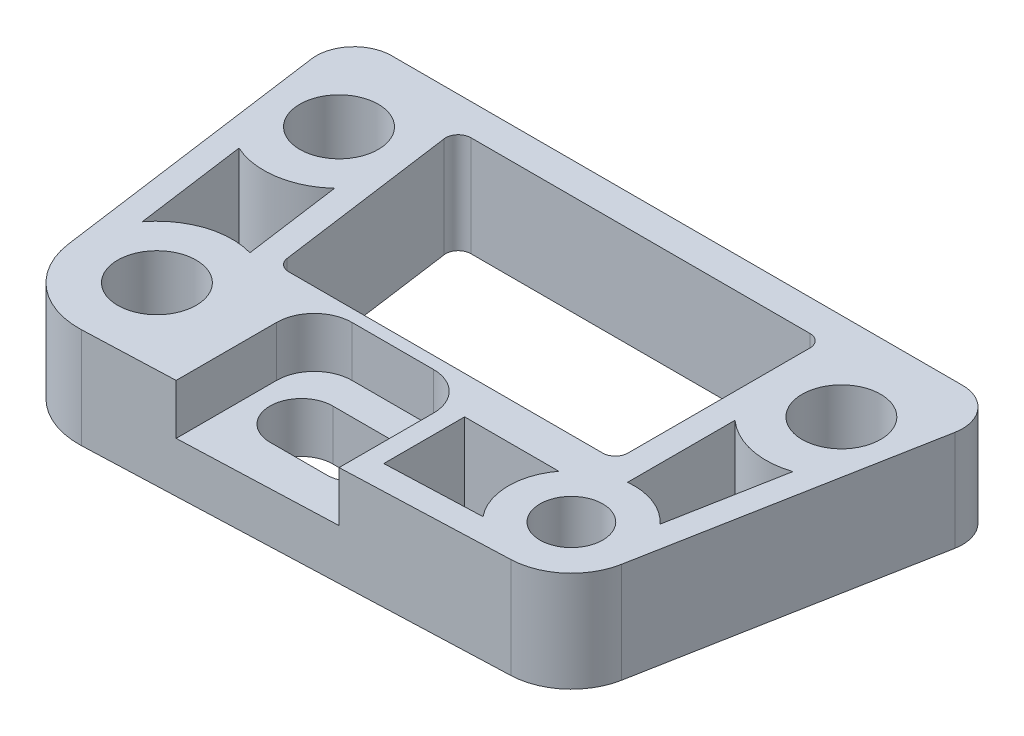
SolidWorks part; units mm, degrees
note: '?' marks a value the reader was unsure of.
material "7075-T6 (SN)"
ref_plane "X-Y Datum" through (0, 0, 0) normal (0, 0, 1) x (1, 0, 0)
ref_plane "X-Z Datum" through (0, 0, 0) normal (0, 1, 0) x (1, 0, 0)
ref_plane "Y-Z Datum" through (0, 0, 0) normal (1, 0, 0) x (0, 0, -1)
other "Graphic1"
other "Graphic (Closed) -1"
other "Graphic2"
other "Graphic (Closed) -2"
sketch "Sketch1" plane through (0, 0, 0) normal (0, 1, 0) x (1, 0, 0)
  line L0 (38.1, -5.08) -> (6.099, -5.08)
  line L1 (54.2925, 13.97) -> (-12.3825, 13.97) construction
  line L4 (54.2925, 31.75) -> (-12.3825, 31.75)
  line L6 (46.355, 22.86) -> (-4.445, 22.86) construction
  line L7 (54.2925, 31.75) -> (54.2925, 13.97)
  line L8 (-12.3825, 31.75) -> (-12.3825, 13.97)
  line L19 (48.26, 0) -> (54.2925, 13.97)
  line L21 (-7.9375, 0) -> (-12.3825, 13.97)
  line L28 (17.1395, -0.1867) -> (14.8786, 3.0422)
  line L30 (16.5708, 1.8211) -> (13.97, 0) construction
  line L31 (16.009, 1.4277) -> (11.1341, 1.4277) construction
  circle A0 centre (0, 0) radius 3.9688
  circle A1 centre (41.91, 0) radius 3.175
  circle A2 centre (46.355, 22.86) radius 3.9688
  circle A3 centre (-4.445, 22.86) radius 3.9687
  arc A4 (48.26, 0) -> (38.1, -5.08) centre (41.91, 0) cw
  arc A5 (6.099, -5.08) -> (-7.9375, 0) centre (0, 0) cw
  arc A12 (17.1395, -0.1867) -> (14.8786, 3.0422) centre (13.97, 0) cw
  point P22 (16.009, 1.4277)
  dimension "D2" = 6.35
  dimension "D7" = 7.9375
  dimension "D8" = 6.35
  dimension "D12" = 0.6858
  dimension "D10" = 7.9375
  dimension "D17" = 35
  dimension "D19" = 7.9375
  dimension "D18" = 19.05
  dimension "D14" = 3.9418
  dimension "D20" = 7.9375
  dimension "D3" = 50.8
  dimension "D4" = 17.78
  dimension "D5" = 8.89
  dimension "D6" = 31.75
  dimension "D9" = 41.91
  dimension "D11" = 7.9375
  dimension "D13" = 3.175
  dimension "D15" = 13.97
  dimension "D16" = 5.08
  dimension "D21" = 4.445
  dimension "D22" = 66.644
  dimension "D23" = 72.35
extrude "Boss-Extrude1" [suppressed] add sketch "Sketch1" against normal blind 10.16
sketch "Sketch2" [suppressed] plane through (0, 0, 0) normal (0, -1, 0) x (1, 0, 0)
  line L0 (9.2075, 0) -> (9.2075, 5.08)
  line L1 (6.099, 5.08) -> (38.1, 5.08) construction
  line L2 (9.2075, 5.08) -> (18.7325, 5.08)
  line L3 (18.7325, 5.08) -> (18.7325, 0)
  arc A0 (9.2075, 0) -> (18.7325, 0) centre (13.97, 0) ccw
  dimension "D1" = 9.525
extrude "Cut-Extrude1" [suppressed] cut sketch "Sketch2" along normal blind 5.08
ref_point "Point1" [suppressed]
ref_point "Point2" [suppressed]
ref_axis "Axis4" [suppressed] through (0, -10.16, 0) along (0, 1, 0)?
sketch "Sketch3" plane through (0, 0, 0) normal (0, 1, 0) x (1, 0, 0)
  line L0 (14.605, 0) -> (11.43, 0) construction
  line L1 (17.7745, -0.1867) -> (15.5136, 3.0422) construction
  line L2 (16.644, 1.4277) -> (14.605, 0) construction
  line L3 (54.2925, 31.75) -> (-12.3825, 31.75)
  line L5 (-12.3825, 13.97) -> (54.2925, 13.97) construction
  line L10 (54.2925, 22.86) -> (46.355, 22.86) construction
  line L11 (46.355, 22.86) -> (-4.445, 22.86) construction
  line L12 (-4.445, 22.86) -> (-12.3825, 22.86) construction
  line L18 (38.735, 8.89) -> (38.735, 27.305)
  line L19 (37.465, 28.575) -> (3.175, 28.575)
  line L20 (1.9169, 27.1318) -> (4.4516, 8.7168)
  line L21 (5.7097, 7.62) -> (37.465, 7.62)
  line L25 (20.32, 0) -> (14.605, 0) construction
  line L26 (20.32, 3.175) -> (14.605, 3.175)
  line L28 (20.32, -3.175) -> (14.605, -3.175)
  line L29 (23.4895, -0.1867) -> (21.2286, 3.0422)
  line L30 (20.32, 0) -> (22.359, 1.4277) construction
  line L31 (42.1505, -6.3454) -> (0.3007, -7.9318)
  line L36 (-7.8634, -1.0823) -> (-12.3825, 31.75)
  line L42 (46.587, 4.2951) -> (48.6976, 15.609)
  line L44 (41.275, 17.1804) -> (41.275, 6.3182)
  line L45 (-6.0805, 4.5926) -> (-7.6429, 15.9435)
  line L46 (2.0783, 7.3311) -> (0.7129, 17.2511)
  line L47 (36.978, -3.9997) -> (27.305, -4.3664)
  line L48 (36.83, 3.81) -> (27.305, 3.81)
  line L49 (27.305, -4.3664) -> (27.305, 3.81)
  line L51 (54.2925, 31.75) -> (48.1523, -1.1645)
  circle A0 centre (0, 0) radius 3.9687
  circle A1 centre (-4.445, 22.86) radius 3.9688
  circle A2 centre (46.355, 22.86) radius 3.9687
  circle A3 centre (41.91, 0) radius 3.175
  arc A4 (15.5136, 3.0422) -> (17.7745, -0.1867) centre (14.605, 0) ccw construction
  arc A5 (48.1523, -1.1645) -> (42.1505, -6.3454) centre (41.91, 0) cw
  arc A6 (0.3007, -7.9318) -> (-7.8634, -1.0823) centre (0, 0) cw
  arc A10 (4.4516, 8.7168) -> (5.7097, 7.62) centre (5.7097, 8.89) ccw
  arc A11 (1.9169, 27.1318) -> (3.175, 28.575) centre (3.175, 27.305) cw
  arc A12 (37.465, 28.575) -> (38.735, 27.305) centre (37.465, 27.305) cw
  arc A13 (37.465, 7.62) -> (38.735, 8.89) centre (37.465, 8.89) ccw
  arc A17 (21.2286, 3.0422) -> (23.4895, -0.1867) centre (20.32, 0) ccw construction
  arc A19 (20.32, -3.175) -> (23.4895, -0.1867) centre (20.32, 0) ccw
  arc A21 (21.2286, 3.0422) -> (20.32, 3.175) centre (20.32, 0) ccw
  arc A24 (46.587, 4.2951) -> (41.275, 6.3182) centre (41.91, 0) ccw
  arc A25 (48.6976, 15.609) -> (41.275, 17.1804) centre (46.355, 22.86) cw
  arc A26 (2.0783, 7.3311) -> (-6.0805, 4.5926) centre (0, 0) ccw
  arc A27 (-7.6429, 15.9435) -> (0.7129, 17.2511) centre (-4.445, 22.86) ccw
  arc A28 (36.978, -3.9997) -> (36.83, 3.81) centre (41.91, 0) cw
  arc A29 (14.605, -3.175) -> (14.605, 3.175) centre (14.605, 0) cw
  point P44 (4.6025, 7.62)
  point P47 (1.7182, 28.575)
  point P52 (38.735, 7.62)
  dimension "D1" = 7.9375
  dimension "D2" = 7.9375
  dimension "D3" = 6.35
  dimension "D4" = 6.35
  dimension "D14" = 7.9375
  dimension "D16" = 6.35
  dimension "D23" = 1.27
  dimension "D24" = 7.9375
  dimension "D26" = 5.715
  dimension "D27" = 145
  dimension "D28" = 7.62
  dimension "D29" = 6.35
  dimension "D32" = 7.62
  dimension "D34" = 7.62
  dimension "D36" = 6.35
  dimension "D5" = 2.4892
  dimension "D6" = 22.86
  dimension "D7" = 145
  dimension "D8" = 7.9375
  dimension "D9" = 41.91
  dimension "D10" = 14.605
  dimension "D11" = 50.8
  dimension "D12" = 17.78
  dimension "D13" = 4.445
  dimension "D15" = 8.89
  dimension "D17" = 3.175
  dimension "D18" = 7.62
  dimension "D19" = 8.89
  dimension "D20" = 7.62
  dimension "D22" = 2.54
  dimension "D25" = 2.54
  dimension "D30" = 2.54
  dimension "D31" = 2.54
  dimension "D33" = 2.4892
  dimension "D35" = 2.54
  dimension "D37" = 3.81
  dimension "D38" = 9.525
extrude "Boss-Extrude4" add sketch "Sketch3" along normal blind 10.16
sketch "Sketch5" plane through (0, 10.16, 0) normal (0, 1, 0) x (1, 0, 0)
  line L0 (25.4, 2.5779) -> (25.4, -7.5821)
  line L1 (21.59, 6.3879) -> (13.335, 6.3879)
  line L2 (25.4, -7.5821) -> (9.525, -7.5821)
  line L3 (9.525, -7.5821) -> (9.525, 2.5779)
  line L4 (17.4625, -3.175) -> (17.4625, -7.5821) construction
  line L5 (0.3007, -7.9318) -> (42.1505, -6.3454) construction
  line L6 (14.605, -3.175) -> (20.32, -3.175) construction
  arc A4 (9.525, 2.5779) -> (13.335, 6.3879) centre (13.335, 2.5779) cw
  arc A5 (21.59, 6.3879) -> (25.4, 2.5779) centre (21.59, 2.5779) cw
  point P18 (17.4625, -7.5821)
  dimension "D1" = 15.875
  dimension "D2" = 3.81
  dimension "D3" = 13.97
extrude "Cut-Extrude3" cut sketch "Sketch5" against normal blind 5.08
ref_point "Point3"
ref_point "Point4"
fillet "Fillet1" radius 3.81 2 edges at (-12.3825, 5.08, -31.75) (54.2925, 5.08, -31.75)
